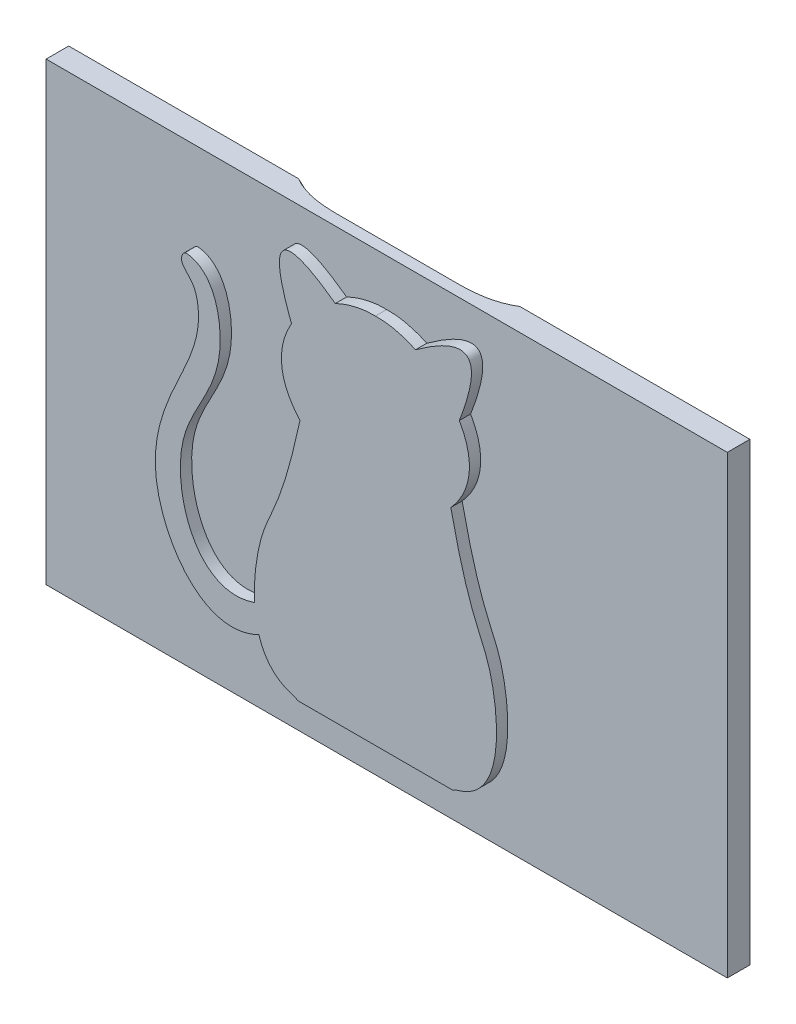
SolidWorks part; units mm, degrees
ref_plane "Front Plane" through (0, 0, 0) normal (0, 0, 1) x (1, 0, 0)
ref_plane "Top Plane" through (0, 0, 0) normal (0, 1, 0) x (1, 0, 0)
ref_plane "Right Plane" through (0, 0, 0) normal (1, 0, 0) x (0, 0, -1)
sketch "Sketch1" plane through (0, 0, 0) normal (0, 0, 1) x (1, 0, 0)
  line L0 (0, 0) -> (0, 40000) construction
  line L1 (-30150, 20150) -> (30150, 20150)
  line L2 (-30150, 20150) -> (-30150, -20150)
  line L3 (-30150, -20150) -> (30150, -20150)
  line L4 (30150, 20150) -> (30150, -20150)
  line L5 (-30150, 20150) -> (30150, -20150) construction
  line L6 (-30150, -20150) -> (30150, 20150) construction
  arc A1 (9797.959, 20150) -> (-9797.959, 20150) centre (0, 30150) cw
  point P0 (0, 0)
  dimension "D3" = 14000
  dimension "D5" = 40000
  dimension "D4" = 10000
  dimension "D1" = 60300
  dimension "D2" = 40300
extrude "MainPlate" add sketch "Sketch1" along normal blind 2000 contours L1 A1 L2 L3 L4 region at (0, -420.7569, 0)
extrude "Notch" add sketch "Sketch1<3>" against normal blind 1000 from surface contours A1 L1 region at (0, 18528.6324, 0) starting at face at (0, 6050, 2000)
sketch "Sketch1<3>" plane through (0, 0, 0) normal (0, 0, 1) x (1, 0, 0) same geometry as "Sketch1"
fillet "NotchFillet" radius 4000 1 edges at (0, 16150, 1000)
sketch "Sketch2" plane through (0, 0, 2000) normal (0, 0, 1) x (1, 0, 0)
  line L0 (0, 20150) -> (0, -20150) construction
  line L1 (-30150, 20150) -> (30150, 20150) construction
  line L2 (-30150, -20150) -> (30150, -20150) construction
  line L3 (-6873.53, -16899.9734) -> (6873.53, -16899.9734)
  spline S0 degree 3 poles (0, 16021.3105) (-5236.0294, 16166.0602) (-11298.7267, 9807.386) (-6676.0754, 4682.9942) knots 0 0 0 0 1 1 1 1
  spline S1 degree 3 poles (-6676.0754, 4682.9942) (-8517.1188, -3858.0319) (-10479.6715, -3136.2316) (-11366.3587, -15716.5622) (-7098.2019, -16739.7346) (-6873.53, -16899.9734) knots 0 0 0 0 0.530593 0.981483 1 1 1 1
  spline S2 degree 2 poles (-3548.1227, 15210.2003) (-10798.6264, 20491.6881) (-7427.6498, 11726.3099) knots 0 0 0 1 1 1
  spline S3 degree 3 poles (6676.0754, 4682.9942) (8517.1188, -3858.0319) (10479.6715, -3136.2316) (11366.3587, -15716.5622) (7098.2019, -16739.7346) (6873.53, -16899.9734) knots 0 0 0 0 0.530593 0.981483 1 1 1 1
  spline S4 degree 2 poles (3548.1227, 15210.2003) (10798.6264, 20491.6881) (7427.6498, 11726.3099) knots 0 0 0 1 1 1
  spline S5 degree 3 poles (0, 16021.3105) (5236.0294, 16166.0602) (11298.7267, 9807.386) (6676.0754, 4682.9942) knots 0 0 0 0 1 1 1 1
  spline S6 degree 3 poles (-10701.4154, -11295.0991) (-15811.5028, -13035.486) (-19505.2983, -2003.0705) (-12595.1441, 4316.2838) (-14193.3304, 12218.8685) (-17013.9673, 12506.8574) (-17294.0971, 11747.5111) (-16814.7225, 11104.5486) (-16001.3411, 10377.595) (-15085.5433, 6773.9322) (-18212.2035, 1514.9564) (-21021.3951, -7650.6943) (-15118.8038, -15967.3219) (-10319.8205, -13558.5924) knots 0 0 0 0 0.209738 0.351877 0.464529 0.468875 0.481926 0.491092 0.507 0.534381 0.661271 0.783505 1 1 1 1
  point P21 (0, -16899.9734)
extrude "Boss-Extrude1" add sketch "Sketch2" along normal blind 1000 contours S1 S6 | L0 S0 S1 L3 | S5 L0 L3 S3 | S4 S5 | S0 S2 region at (4392.2, -2088.4466, 2000) region at (-4392.1804, -2088.9505, 2000) region at (-6640.8068, 14998.3265, 2000) region at (6640.8068, 14998.3265, 2000) region at (-16535.272, 11256.528, 2000)
